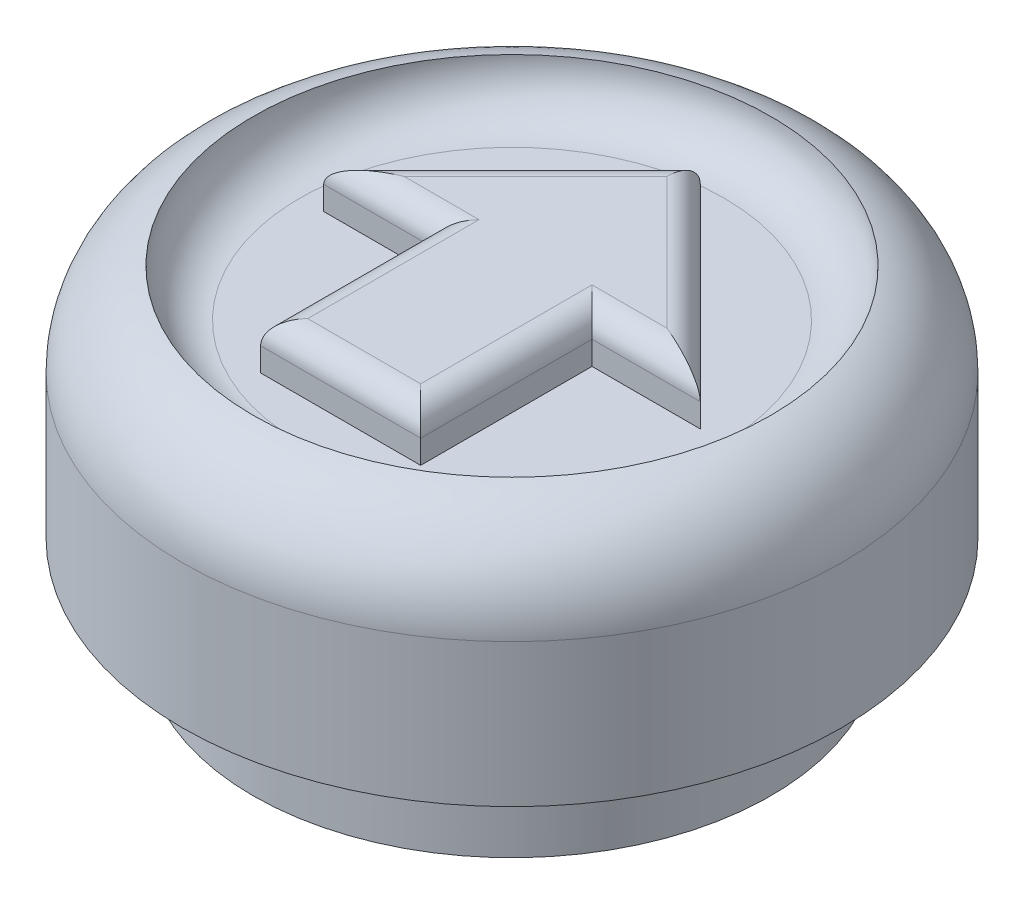
SolidWorks part; units mm, degrees
ref_plane "Спереди" through (0, 0, 0) normal (0, 0, 1) x (1, 0, 0)
ref_plane "Сверху" through (0, 0, 0) normal (0, 1, 0) x (1, 0, 0)
ref_plane "Справа" through (0, 0, 0) normal (1, 0, 0) x (0, 0, -1)
sketch "Эскиз1" plane through (0, 0, 0) normal (0, 1, 0) x (1, 0, 0)
  circle A0 centre (0, 0) radius 5.5
extrude "Бобышка-Вытянуть1" add sketch "Эскиз1" along normal blind 7
sketch "Эскиз6" plane through (0, 0, 0) normal (0, 0, 1) x (1, 0, 0)
  line L0 (-1000, 0) -> (49000, 0) construction
  line L1 (-5.5, 0) -> (5.5, 0) construction
  line L2 (0, -1000) -> (0, 49000) construction
  line L3 (-7, -1000) -> (-7, 49000) construction
  line L4 (-999.6295, 7) -> (49000.3705, 7) construction
  line L6 (-999.6295, 3) -> (49000.3705, 3) construction
  line L11 (-5.5, -993) -> (-5.5, 49007) construction
  line L12 (-4.6652, 2) -> (-7, 2)
  line L13 (-5.5, 7) -> (-4.6652, 7)
  line L14 (-4.6652, 7) -> (-4.6652, 3)
  line L16 (-7, 3) -> (-7, 5.0359)
  line L17 (-4.6652, 3) -> (-4.6652, 2)
  line L18 (-7, 2) -> (-7, 3)
  circle A2 centre (-4.9641, 5.0359) radius 2.0359 construction
  arc A3 (-7, 5.0359) -> (-5.5, 7) centre (-4.9641, 5.0359) cw
  point P5 (0, 0)
  point P15 (-5.5, 7)
revolve "Повернуть3" add sketch "Эскиз6" angle 360 about L2
sketch "Эскиз2" plane through (0, 7, 0) normal (0, 1, 0) x (1, 0, 0)
  circle A0 centre (0, 0) radius 5.5
extrude "Вырез-Вытянуть1" cut sketch "Эскиз2" against normal blind 1
sketch "Эскиз3" plane through (0, 6, 0) normal (0, 1, 0) x (1, 0, 0)
  line L0 (-1000, 0) -> (49000, 0) construction
  line L1 (0, -1000) -> (0, 49000) construction
  line L2 (1.7, -1000) -> (1.7, 49000) construction
  line L3 (-1.7, -1000) -> (-1.7, 49000) construction
  line L4 (-1000, -3.6401) -> (49000, -3.6401) construction
  line L5 (-1000, 4) -> (49000, 4) construction
  line L6 (-4, -1000) -> (-4, 49000) construction
  line L7 (4, -1000) -> (4, 49000) construction
  line L8 (0, 4) -> (-4, 0)
  line L9 (-4, 0) -> (-1.7, 0)
  line L10 (-1.7, 0) -> (-1.7, -3.6401)
  line L11 (-1.7, -3.6401) -> (1.7, -3.6401)
  line L12 (1.7, -3.6401) -> (1.7, 0)
  line L13 (1.7, 0) -> (4, 0)
  line L14 (4, 0) -> (0, 4)
  line L15 (-1.7, -1000) -> (-1.7, 49000) construction
  line L16 (1.7, -1000) -> (1.7, 49000) construction
extrude "Бобышка-Вытянуть2" add sketch "Эскиз3" along normal blind 1
sketch "Эскиз5" plane through (0, 0, 0) normal (0, -1, 0) x (1, 0, 0)
  line L0 (0, -1000) -> (0, 49000) construction
  line L1 (-1000, 0) -> (49000, 0) construction
  line L2 (-2, -2) -> (2, -2)
  line L3 (2, -2) -> (2, 2)
  line L4 (-2, 2) -> (2, 2)
  line L5 (-2, -2) -> (-2, 2)
  line L7 (-2, -1000) -> (-2, 49000) construction
  line L8 (2, -1000) -> (2, 49000) construction
  line L9 (-1000, 2) -> (49000, 2) construction
  line L10 (-1000, -2) -> (49000, -2) construction
  dimension "D1" = 2
  dimension "D2" = 2
extrude "Вырез-Вытянуть2" cut sketch "Эскиз5" against normal blind 3
fillet "Скругление3" radius 1 1 edges at (0, 6, 5.5)
fillet "Скругление4" radius 0.5 7 edges at (-2.85, 7, 0) (-2, 7, -2) (2, 7, -2) (2.85, 7, 0) (1.7, 7, 1.8201) (0, 7, 3.6401) (-1.7, 7, 1.8201)
